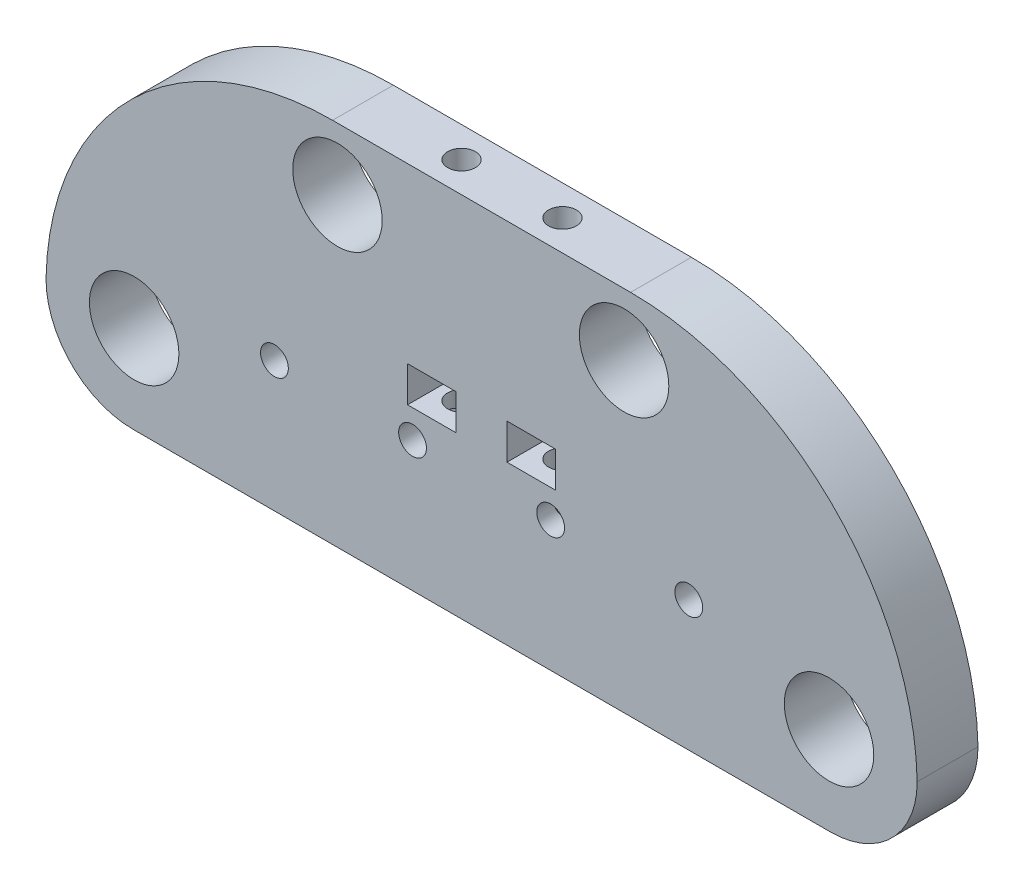
SolidWorks part; units mm, degrees
ref_plane "Plano frontal" through (0, 0, 0) normal (0, 0, 1) x (1, 0, 0)
ref_plane "Plano superior" through (0, 0, 0) normal (0, 1, 0) x (1, 0, 0)
ref_plane "Plano direito" through (0, 0, 0) normal (1, 0, 0) x (0, 0, -1)
sketch "Esboço1" plane through (0, 0, 0) normal (0, 0, 1) x (1, 0, 0)
  line L0 (-39.9126, -26.5911) -> (40.0874, -26.5911) construction
  line L5 (-19.1243, 10.7089) -> (50.2374, -28.131) construction
  line L6 (-50.0626, -27.9516) -> (19.1801, 10.7089) construction
  line L7 (-11.3586, 3.5589) -> (11.3414, 3.5589) construction
  line L9 (-39.9126, -26.5911) -> (-39.9126, -31.5911) construction
  line L10 (-11.3586, 3.5589) -> (-11.3586, 8.4072) construction
  line L16 (0.0874, 10.7089) -> (0.0874, -31.5911) construction
  line L17 (-50.0626, -31.5911) -> (50.2374, -31.5911)
  line L22 (-45.0626, -21.4411) -> (-50.0626, -21.4411) construction
  line L23 (0.0874, 5.2627) -> (-11.3586, 5.2627) construction
  line L32 (-50.0626, 10.7089) -> (-50.0626, -31.5911)
  line L35 (45.2374, -21.4411) -> (50.2374, -21.4411) construction
  line L44 (50.2374, 10.7089) -> (50.2374, -31.5911)
  line L45 (-16.5086, 8.7089) -> (-16.5086, 10.7089) construction
  line L54 (-2.8356, -13.3411) -> (-8.4356, -13.3411)
  line L61 (-50.0626, -16.68) -> (50.2374, -16.68) construction
  line L69 (3.0104, -9.2411) -> (8.6104, -9.2411)
  line L70 (5.8104, 10.7089) -> (5.8104, -11.2911) construction
  line L74 (3.0104, -9.2411) -> (3.0104, -13.3411)
  line L80 (-50.0626, 10.7089) -> (50.2374, 10.7089)
  line L82 (-16.5086, -1.5911) -> (16.4914, -1.5911) construction
  line L83 (3.0104, -13.3411) -> (8.6104, -13.3411)
  line L84 (8.6104, -9.2411) -> (8.6104, -13.3411)
  line L85 (3.0104, -9.2411) -> (8.6104, -13.3411) construction
  line L86 (3.0104, -13.3411) -> (8.6104, -9.2411) construction
  line L87 (-8.4356, -9.2411) -> (-8.4356, -13.3411)
  line L88 (-2.8356, -9.2411) -> (-8.4356, -9.2411)
  line L89 (-2.8356, -9.2411) -> (-2.8356, -13.3411)
  line L90 (15.9874, -16.5911) -> (0.0874, -16.5911) construction
  line L91 (15.9874, -16.5911) -> (15.9874, -31.5911) construction
  line L92 (50.2374, 10.7089) -> (50.2374, -31.5911)
  line L93 (-50.0626, 10.7089) -> (-50.0626, -31.5911)
  circle A7 centre (-16.5086, 3.5589) radius 5.15
  circle A8 centre (16.4914, 3.5589) radius 5.15
  circle A17 centre (-39.9126, -21.4411) radius 5.15
  circle A18 centre (40.0874, -21.4411) radius 5.15
  circle A19 centre (8.0374, -16.5911) radius 1.6
  circle A20 centre (23.9374, -16.5911) radius 1.6
  circle A21 centre (-7.8626, -16.5911) radius 1.6
  circle A22 centre (-23.7626, -16.5911) radius 1.6
  point P0 (0, 0)
  dimension "D6" = 10.3
  dimension "D9" = 2
  dimension "D8" = 5.6
  dimension "D7" = 10.3
  dimension "D11" = 3.2
  dimension "D1" = 5
  dimension "D2" = 5
  dimension "D3" = 5
  dimension "D4" = 15
  dimension "D5" = 22.7
  dimension "D10" = 4.1
extrude "Ressalto-extrusão1" add sketch "Esboço1" along normal blind 7
fillet "Filete1" radius 10 2 edges at (50.2374, -31.5911, 3.5) (-50.0626, -31.5911, 3.5)
sketch "Esboço4" plane through (0, 10.7089, 0) normal (0, 1, 0) x (1, 0, 0)
  line L0 (0.0874, 0) -> (0.0874, -7) construction
  line L1 (-50.0626, 0) -> (50.2374, 0) construction
  line L2 (-50.0626, -7) -> (50.2374, -7) construction
  line L3 (0.0874, -3.5) -> (-5.7226, -3.5) construction
  circle A0 centre (-5.7226, -3.5) radius 1.6
  circle A1 centre (5.8974, -3.5) radius 1.6
  dimension "D2" = 3.2
  dimension "D1" = 5.81
extrude "Corte-extrusão3" cut sketch "Esboço4" against normal through all
fillet "Filete3" radius 33 2 edges at (50.2374, 10.7089, 3.5) (-50.0626, 10.7089, 3.5)
